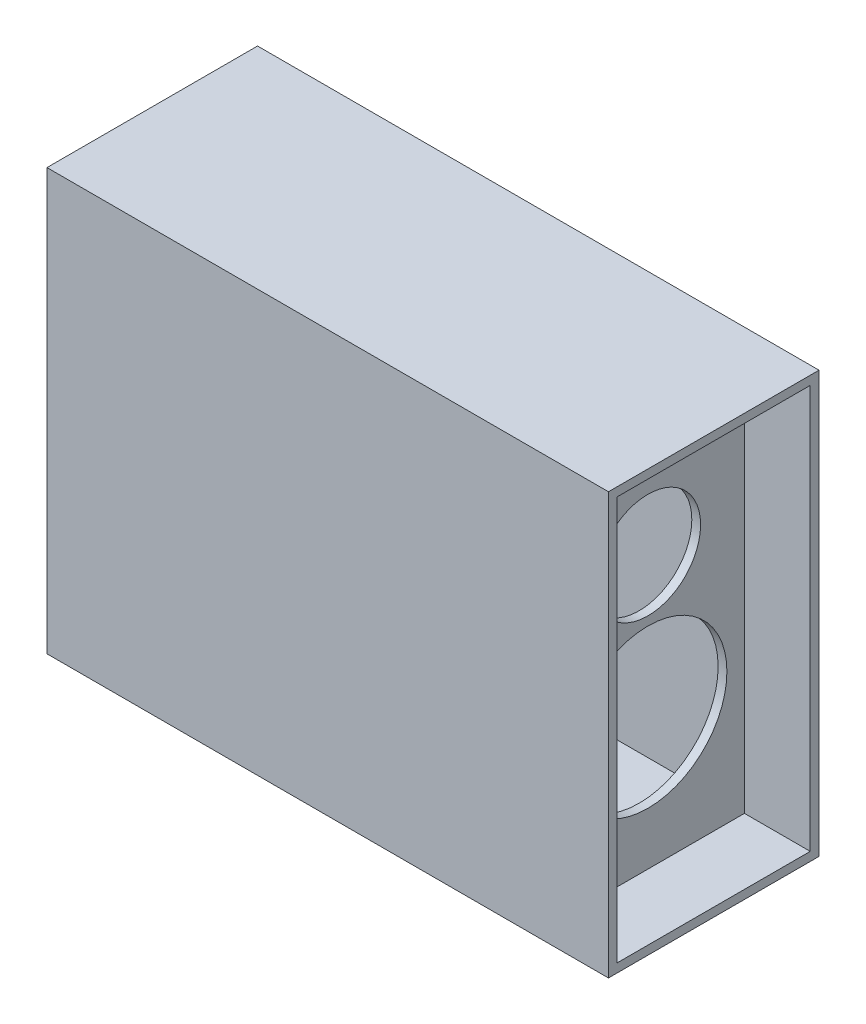
SolidWorks part; units mm, degrees
ref_plane "Front Plane" through (0, 0, 0) normal (1, 0, 0) x (0, 1, 0)
ref_plane "Top Plane" through (0, 0, 0) normal (0, 0, 1) x (0, 1, 0)
ref_plane "Right Plane" through (0, 0, 0) normal (0, 1, 0) x (-1, 0, 0)
sketch "Sketch2" plane through (0, 0, 0) normal (1, 0, 0) x (0, 1, 0)
  line L1 (-70.2342, 35.2527) -> (82.1658, 35.2527)
  line L2 (-70.2342, 35.2527) -> (-70.2342, -40.9473)
  line L3 (-70.2342, -40.9473) -> (82.1658, -40.9473)
  line L4 (82.1658, 35.2527) -> (82.1658, -40.9473)
  dimension "D1" = 76.2
  dimension "D2" = 152.4
extrude "Boss-Extrude1" add sketch "Sketch2" along normal blind 3.175
sketch "Sketch3" plane through (3.175, 0, 0) normal (1, 0, 0) x (0, 1, 0)
  line L0 (82.1658, 35.2527) -> (-70.2342, 35.2527) construction
  line L1 (-70.2342, 35.2527) -> (82.1658, 35.2527)
  line L2 (-70.2342, 35.2527) -> (-70.2342, -40.9473)
  line L3 (-70.2342, -40.9473) -> (82.1658, -40.9473)
  line L4 (82.1658, 35.2527) -> (82.1658, -40.9473)
  line L5 (82.1658, -40.9473) -> (82.1658, 35.2527) construction
  line L6 (-70.2342, -40.9473) -> (82.1658, -40.9473) construction
  line L7 (-70.2342, 35.2527) -> (-70.2342, -40.9473) construction
  line L9 (-67.0592, 32.0777) -> (78.9908, 32.0777)
  line L10 (-67.0592, 32.0777) -> (-67.0592, -37.7723)
  line L11 (-67.0592, -37.7723) -> (78.9908, -37.7723)
  line L12 (78.9908, 32.0777) -> (78.9908, -37.7723)
  dimension "D1" = 0
  dimension "D2" = 0
  dimension "D3" = 0
  dimension "D4" = 0
  dimension "D5" = 3.175
  dimension "D6" = 3.175
  dimension "D7" = 3.175
  dimension "D8" = 3.175
extrude "Boss-Extrude2" add sketch "Sketch3" along normal blind 71.4375
sketch "Sketch4" plane through (74.6125, 0, 0) normal (1, 0, 0) x (0, 1, 0)
  line L0 (82.1658, 35.2527) -> (-70.2342, 35.2527) construction
  line L1 (-70.2342, 35.2527) -> (82.1658, 35.2527)
  line L2 (-70.2342, 35.2527) -> (-70.2342, -40.9473)
  line L3 (-70.2342, -40.9473) -> (82.1658, -40.9473)
  line L4 (82.1658, 35.2527) -> (82.1658, -40.9473)
  line L5 (-70.2342, 35.2527) -> (-70.2342, -40.9473) construction
  line L6 (82.1658, -40.9473) -> (82.1658, 35.2527) construction
  line L7 (-70.2342, -40.9473) -> (82.1658, -40.9473) construction
  dimension "D1" = 0
  dimension "D2" = 0
  dimension "D3" = 0
  dimension "D4" = 0
extrude "Boss-Extrude3" add sketch "Sketch4" along normal blind 3.175
sketch "Sketch5" plane through (77.7875, 0, 0) normal (1, 0, 0) x (0, 1, 0)
  line L0 (82.1658, 35.2527) -> (-70.2342, 35.2527) construction
  line L1 (-70.2342, 35.2527) -> (82.1658, 35.2527)
  line L2 (-70.2342, 35.2527) -> (-70.2342, -40.9473)
  line L3 (-70.2342, -40.9473) -> (82.1658, -40.9473)
  line L4 (82.1658, 35.2527) -> (82.1658, -40.9473)
  line L5 (-70.2342, 35.2527) -> (-70.2342, -40.9473) construction
  line L6 (-70.2342, -40.9473) -> (82.1658, -40.9473) construction
  line L7 (82.1658, -40.9473) -> (82.1658, 35.2527) construction
  line L9 (-67.0592, 32.0777) -> (78.9908, 32.0777)
  line L10 (-67.0592, 32.0777) -> (-67.0592, -37.7723)
  line L11 (-67.0592, -37.7723) -> (78.9908, -37.7723)
  line L12 (78.9908, 32.0777) -> (78.9908, -37.7723)
  dimension "D1" = 0
  dimension "D2" = 0
  dimension "D3" = 0
  dimension "D4" = 0
  dimension "D5" = 3.175
  dimension "D6" = 3.175
  dimension "D7" = 3.175
  dimension "D8" = 3.175
extrude "Boss-Extrude4" add sketch "Sketch5" along normal blind 98.425
sketch "Sketch6" plane through (176.2125, 0, 0) normal (1, 0, 0) x (0, 1, 0)
  line L0 (82.1658, 35.2527) -> (-70.2342, 35.2527) construction
  line L1 (-70.2342, 35.2527) -> (82.1658, 35.2527)
  line L2 (-70.2342, 35.2527) -> (-70.2342, -40.9473)
  line L3 (-70.2342, -40.9473) -> (82.1658, -40.9473)
  line L4 (82.1658, 35.2527) -> (82.1658, -40.9473)
  line L5 (-70.2342, 35.2527) -> (-70.2342, -40.9473) construction
  line L6 (-70.2342, -40.9473) -> (82.1658, -40.9473) construction
  line L7 (82.1658, -40.9473) -> (82.1658, 35.2527) construction
  dimension "D1" = 0
  dimension "D2" = 0
  dimension "D3" = 0
  dimension "D4" = 0
hole_wizard "#97 (1) Diameter Hole1" positions "Sketch7" profile "Sketch9" hole size "#97" standard "ANSI Inch" end condition through all
sketch "Sketch7" plane through (77.7875, 0, 0) normal (1, 0, 0) x (0, 1, 0)
  line L0 (-70.2342, -40.9473) -> (82.1658, -40.9473) construction
  line L1 (82.1658, 35.2527) -> (82.1658, -40.9473) construction
  line L2 (-70.2342, 35.2527) -> (-70.2342, -40.9473) construction
  point P0 (-19.4342, -2.8473)
  point P2 (31.3658, -2.8473)
  dimension "D1" = 38.1
  dimension "D2" = 50.8
  dimension "D3" = 38.1
  dimension "D4" = 50.8
sketch "Sketch9" plane through (77.7875, -19.4342, -2.8473) normal (0, 1, 0) x (0, 0, -1)
  line L0 (0, 0) -> (0, 77.7875)
  line L1 (0, 77.7875) -> (12.7, 77.7875)
  line L2 (12.7, 77.7875) -> (12.7, 0)
  line L5 (12.7, 0) -> (0, 0)
  line L11 (0, -6.35) -> (0, 107.95) construction
  dimension "Thru Hole Dia." = 25.4
  dimension "Thru Hole Depth" = 77.7875
hole_wizard "#97 (1.5) Diameter Hole1" positions "Sketch10" profile "Sketch11" hole size "#97" standard "ANSI Inch"
sketch "Sketch10" plane through (0, 0, 0) normal (-1, 0, 0) x (0, -1, 0)
  line L0 (-82.1658, 35.2527) -> (-82.1658, -40.9473) construction
  line L1 (70.2342, -40.9473) -> (-82.1658, -40.9473) construction
  point P0 (-31.3658, -2.8473)
  dimension "D1" = 50.8
  dimension "D2" = 38.1
sketch "Sketch11" plane through (0, 31.3658, -2.8473) normal (0, 1, 0) x (0, 0, 1)
  line L0 (0, 0) -> (0, 6.35)
  line L1 (0, 6.35) -> (19.05, 6.35)
  line L2 (19.05, 6.35) -> (19.05, 0)
  line L5 (19.05, 0) -> (0, 0)
  line L10 (0, 6.35) -> (-19.05, 6.35) construction
  line L11 (0, -6.35) -> (0, 107.95) construction
  dimension "Hole Dia." = 38.1
  dimension "Hole Depth" = 6.35
  dimension "Drill Angle" = 180
extrude "Boss-Extrude6" add sketch "Sketch6" along normal blind 3.175
hole_wizard "#97 (1.5) Diameter Hole2" positions "Sketch12" profile "Sketch13" hole size "#97" standard "ANSI Inch"
sketch "Sketch12" plane through (179.3875, 0, 0) normal (1, 0, 0) x (0, 1, 0)
  line L0 (82.1658, -40.9473) -> (82.1658, 35.2527) construction
  line L1 (-70.2342, -40.9473) -> (82.1658, -40.9473) construction
  point P0 (31.3658, -2.8473)
  dimension "D1" = 50.8
  dimension "D2" = 38.1
sketch "Sketch13" plane through (179.3875, 31.3658, -2.8473) normal (0, 1, 0) x (0, 0, -1)
  line L0 (0, 0) -> (0, 6.35)
  line L1 (0, 6.35) -> (19.05, 6.35)
  line L2 (19.05, 6.35) -> (19.05, 0)
  line L5 (19.05, 0) -> (0, 0)
  line L10 (0, 6.35) -> (-19.05, 6.35) construction
  line L11 (0, -6.35) -> (0, 107.95) construction
  dimension "Hole Dia." = 38.1
  dimension "Hole Depth" = 6.35
  dimension "Drill Angle" = 180
hole_wizard "#97 (2.25) Diameter Hole1" positions "Sketch14" profile "Sketch15" hole size "#97" standard "ANSI Inch"
sketch "Sketch14" plane through (179.3875, 0, 0) normal (1, 0, 0) x (0, 1, 0)
  line L0 (-70.2342, 35.2527) -> (-70.2342, -40.9473) construction
  line L1 (82.1658, 35.2527) -> (-70.2342, 35.2527) construction
  point P0 (-19.4342, -2.8473)
  dimension "D1" = 50.8
  dimension "D2" = 38.1
sketch "Sketch15" plane through (179.3875, -19.4342, -2.8473) normal (0, 1, 0) x (0, 0, -1)
  line L0 (0, 0) -> (0, 6.35)
  line L1 (0, 6.35) -> (28.575, 6.35)
  line L2 (28.575, 6.35) -> (28.575, 0)
  line L5 (28.575, 0) -> (0, 0)
  line L10 (0, 6.35) -> (-28.575, 6.35) construction
  line L11 (0, -6.35) -> (0, 107.95) construction
  dimension "Hole Dia." = 57.15
  dimension "Hole Depth" = 6.35
  dimension "Drill Angle" = 180
sketch "Sketch16" plane through (179.3875, 0, 0) normal (1, 0, 0) x (0, 1, 0)
  line L0 (82.1658, 35.2527) -> (-70.2342, 35.2527) construction
  line L1 (-70.2342, 35.2527) -> (82.1658, 35.2527)
  line L2 (-70.2342, 35.2527) -> (-70.2342, -40.9473)
  line L3 (-70.2342, -40.9473) -> (82.1658, -40.9473)
  line L4 (82.1658, 35.2527) -> (82.1658, -40.9473)
  line L5 (-70.2342, -40.9473) -> (82.1658, -40.9473) construction
  line L6 (-70.2342, 35.2527) -> (-70.2342, -40.9473) construction
  line L7 (82.1658, -40.9473) -> (82.1658, 35.2527) construction
  line L9 (-67.0592, 32.0777) -> (78.9908, 32.0777)
  line L10 (-67.0592, 32.0777) -> (-67.0592, -37.7723)
  line L11 (-67.0592, -37.7723) -> (78.9908, -37.7723)
  line L12 (78.9908, 32.0777) -> (78.9908, -37.7723)
  dimension "D1" = 0
  dimension "D2" = 0
  dimension "D3" = 0
  dimension "D4" = 0
  dimension "D5" = 3.175
  dimension "D6" = 3.175
  dimension "D7" = 3.175
  dimension "D8" = 3.175
extrude "Boss-Extrude7" add sketch "Sketch16" along normal blind 23.8125
